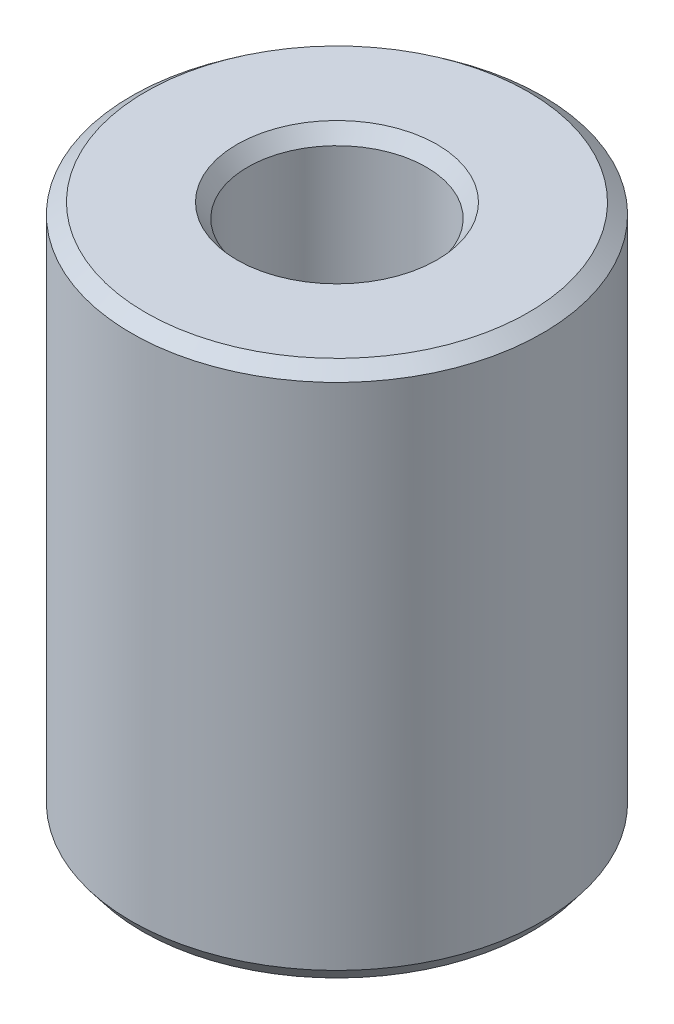
SolidWorks part; units mm, degrees
ref_plane "Front Plane" through (0, 0, 0) normal (0, 0, 1) x (1, 0, 0)
ref_plane "Top Plane" through (0, 0, 0) normal (0, 1, 0) x (1, 0, 0)
ref_plane "Right Plane" through (0, 0, 0) normal (1, 0, 0) x (0, 0, -1)
sketch "Sketch1" plane through (0, 0, 0) normal (0, 1, 0) x (1, 0, 0)
  circle A0 centre (0, 0) radius 57.5
  dimension "SLEEVE_OD" = 115
extrude "Boss-Extrude1" add sketch "Sketch1" along normal blind 149.4769
sketch "Sketch2" plane through (0, 0, 0) normal (0, 1, 0) x (1, 0, 0)
  circle A0 centre (0, 0) radius 24.9768
  dimension "BORE_D" = 49.9535
extrude "Cut-Extrude1" cut sketch "Sketch2" along normal through all
chamfer "Chamfer1" distance 3.0233 angle 52.706 4 edges at (0, 149.4769, 24.9768) (0, 0, 24.9768) (0, 0, 57.5) (0, 149.4769, 57.5) first distance on face at (0, 149.4769, 24.9768) first distance on face at (0, 0, 24.9768) first distance on face at (0, 149.4769, 57.5)
